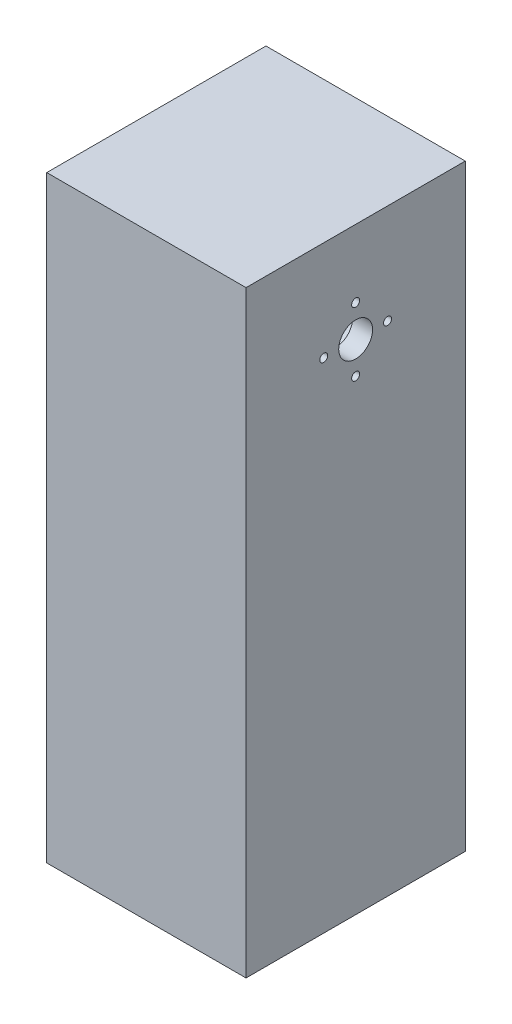
SolidWorks part; units mm, degrees
ref_plane "Front Plane" through (0, 0, 0) normal (0, 0, 1) x (1, 0, 0)
ref_plane "Top Plane" through (0, 0, 0) normal (0, 1, 0) x (1, 0, 0)
ref_plane "Right Plane" through (0, 0, 0) normal (1, 0, 0) x (0, 0, -1)
sketch "Sketch1" plane through (0, 0, 0) normal (0, 0, 1) x (1, 0, 0)
  line L1 (-25, 0) -> (25, 0)
  line L2 (-25, 0) -> (-25, -150)
  line L3 (-25, -150) -> (25, -150)
  line L4 (25, 0) -> (25, -150)
  dimension "D1" = 50
  dimension "D2" = 150
extrude "Boss-Extrude1" add sketch "Sketch1" against normal blind 55
sketch "Sketch2" plane through (25, 0, 0) normal (1, 0, 0) x (0, 0, -1)
  line L0 (55, 0) -> (0, 0) construction
  line L1 (0, -150) -> (0, 0) construction
  circle A0 centre (27.5, -25) radius 10.25
  dimension "D1" = 25
  dimension "D2" = 27.5
extrude "Cut-Extrude1" cut sketch "Sketch2" against normal blind 45 and the other way through all
sketch "Sketch7" plane through (-20, 0, 0) normal (1, 0, 0) x (0, 0, -1)
  line L0 (27.5, -17) -> (27.5, -33) construction
  circle A0 centre (27.5, -25) radius 8
  circle A1 centre (27.5, -17) radius 1
  circle A2 centre (35.5, -25) radius 1
  circle A3 centre (27.5, -33) radius 1
  circle A4 centre (19.5, -25) radius 1
  circle A5 centre (27.5, -25) radius 4.25
  point P14 (27.5, -25)
  dimension "D1" = 16
  dimension "D2" = 2
  dimension "D4" = 8.5
  dimension "D3" = 4
extrude "Cut-Extrude3" cut sketch "Sketch7" against normal blind 10 contours L0 A0 A1 | A0 A1 | A0 L0 A1 | A0 A4 | A0 A4 | L0 A3 A0 | A3 L0 A0 | A0 A3 | A0 A2 | A0 A2 | A5 L0 | L0 A5 region at (-20, -17.4355, -27.9155) region at (-20, -16.587, -27.5) region at (-20, -17.4355, -27.0845) region at (-20, -25, -29.3038) region at (-20, -25, -25.6962) region at (-20, -25, -35.913) region at (-20, -25, -35.0645) region at (-20, -25, -19.9355) region at (-20, -25, -19.087) region at (-20, -32.5645, -27.9155) region at (-20, -32.5645, -27.0845) region at (-20, -33.413, -27.5)
sketch "Sketch8" plane through (-20, 0, 0) normal (1, 0, 0) x (0, 0, -1)
  circle A0 centre (27.5, -25) radius 10.25
  circle A1 centre (27.5, -17) radius 1
  circle A2 centre (27.5, -25) radius 4.25
  circle A3 centre (35.5, -25) radius 1
  circle A4 centre (27.5, -33) radius 1
  circle A5 centre (19.5, -25) radius 1
  point P16 (27.5, -25)
  dimension "D1" = 4
extrude "Boss-Extrude2" add sketch "Sketch8" along normal blind 45
sketch "Sketch9" plane through (-25, 0, 0) normal (-1, 0, 0) x (0, 0, 1)
  circle A0 centre (-27.5, -25) radius 10.25
extrude "Cut-Extrude4" cut sketch "Sketch9" against normal blind 45
